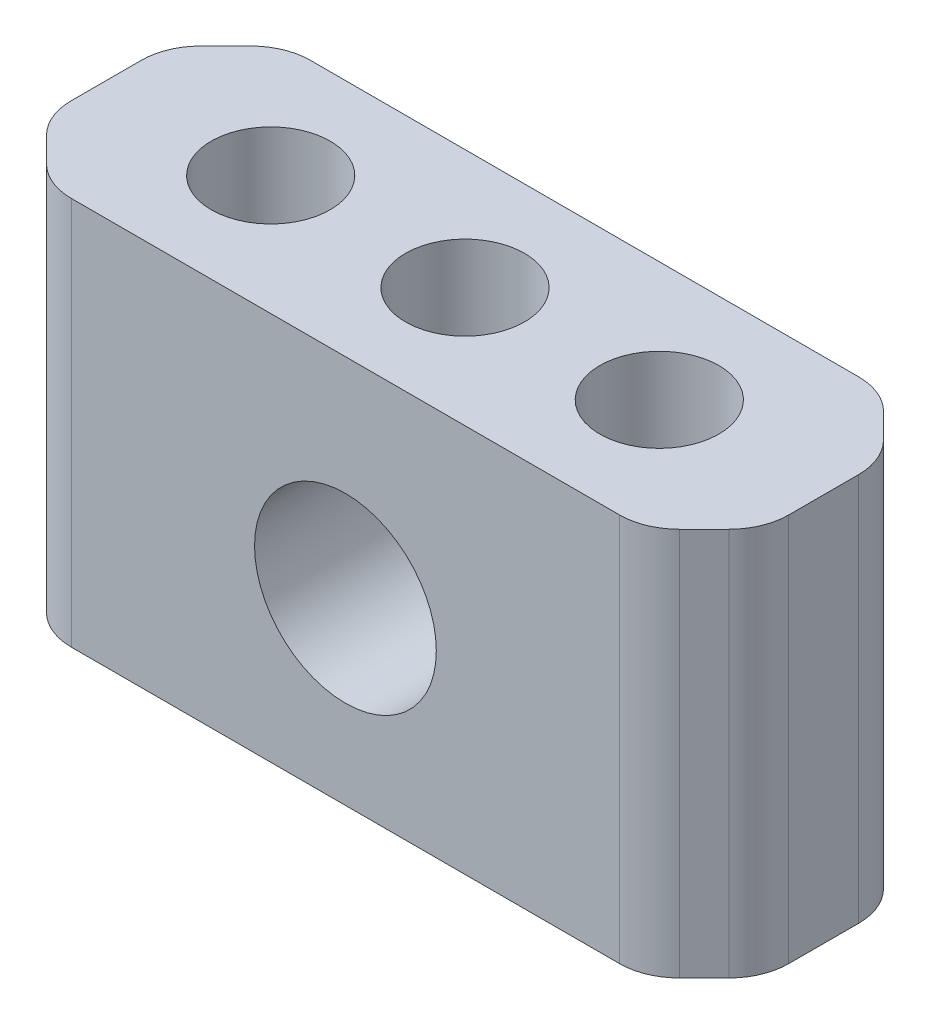
SolidWorks part; units mm, degrees
ref_plane "Front Plane" through (0, 0, 0) normal (0, 0, 1) x (1, 0, 0)
ref_plane "Top Plane" through (0, 0, 0) normal (0, 1, 0) x (1, 0, 0)
ref_plane "Right Plane" through (0, 0, 0) normal (1, 0, 0) x (0, 0, -1)
sketch "Sketch1" plane through (0, 0, 0) normal (0, 0, 1) x (1, 0, 0)
  line L1 (12, -6.5) -> (-12, -6.5)
  line L2 (12, -6.5) -> (12, 6.5)
  line L3 (12, 6.5) -> (-12, 6.5)
  line L4 (-12, -6.5) -> (-12, 6.5)
  line L5 (12, -6.5) -> (-12, 6.5) construction
  line L6 (12, 6.5) -> (-12, -6.5) construction
  point P0 (0, 0)
  dimension "D1" = 24
  dimension "D2" = 13
extrude "Boss-Extrude1" add sketch "Sketch1" along normal blind 4 and the other way blind 4
sketch "Sketch3" plane through (0, 0, 0) normal (0, 0, 1) x (1, 0, 0)
  line L0 (-12, -6.5) -> (12, -6.5) construction
  circle A0 centre (0, -0.5) radius 3.04
  dimension "D1" = 6.08
  dimension "D2" = 6
extrude "Cut-Extrude1" cut sketch "Sketch3" against normal blind 7 and the other way blind 7
sketch "Sketch4" plane through (0, 6.5, 0) normal (0, 1, 0) x (1, 0, 0)
  line L0 (0, 0) -> (0, -4) construction
  line L2 (12, -4) -> (-12, -4) construction
  line L3 (12, 4) -> (-12, 4) construction
  circle A0 centre (-6.5, 0) radius 1.99
  circle A1 centre (6.5, 0) radius 1.99
  circle A2 centre (0, 0) radius 1.99 construction
  dimension "D1" = 3.98
  dimension "D2" = 13
  dimension "D3" = 4
extrude "Cut-Extrude2" cut sketch "Sketch4" against normal blind 10
sketch "Sketch5" plane through (0, 6.5, 0) normal (0, 1, 0) x (1, 0, 0)
  line L0 (-6.5, 0) -> (6.5, 0) construction
  circle A0 centre (0, 0) radius 1.99
  circle A1 centre (-6.5, 0) radius 1.99 construction
extrude "Cut-Extrude4" cut sketch "Sketch5" against normal blind 3.9
chamfer "Chamfer1" distance 2 angle 45 4 edges at (12, 0, 4) (12, 0, -4) (-12, 0, 4) (-12, 0, -4)
fillet "Fillet1" radius 2 8 edges at (10, 0, 4) (-10, 0, 4) (-12, 0, 2) (-12, 0, -2) (-10, 0, -4) (12, 0, 2) (12, 0, -2) (10, 0, -4)
